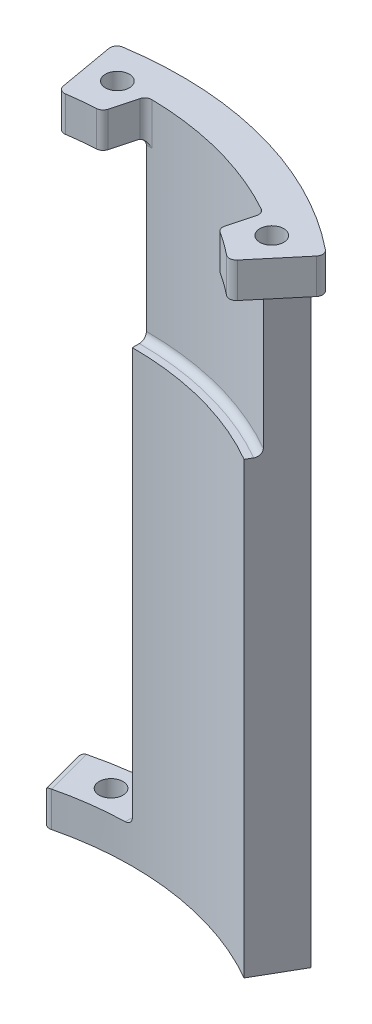
SolidWorks part; units mm, degrees
ref_plane "Front Plane" through (0, 0, 0) normal (0, 0, 1) x (1, 0, 0)
ref_plane "Top Plane" through (0, 0, 0) normal (0, 1, 0) x (1, 0, 0)
ref_plane "Right Plane" through (0, 0, 0) normal (1, 0, 0) x (0, 0, -1)
sketch "Sketch1" plane through (0, 0, 0) normal (0, 1, 0) x (1, 0, 0)
  line L0 (0, 50.5) -> (0, 0) construction
  line L1 (0, 0) -> (25.25, 43.7343) construction
  line L2 (0, 50.5) -> (0, 43.5)
  line L3 (21.75, 37.6721) -> (25.25, 43.7343)
  arc A0 (25.25, 43.7343) -> (0, 50.5) centre (0, 0) ccw
  arc A1 (21.75, 37.6721) -> (0, 43.5) centre (0, 0) ccw
  arc A2 (21.75, 37.6721) -> (0, 43.5) centre (0, 0) ccw construction
  dimension "D3" = 50.5
  dimension "D2" = 30
  dimension "D1" = 7
extrude "Boss-Extrude1" add sketch "Sketch1" along normal blind 94
sketch "Sketch2" plane through (0, 0, 0) normal (0, 1, 0) x (1, 0, 0)
  line L0 (-13.0704, 48.7793) -> (-11.2586, 42.0178)
  line L1 (-6.5916, 50.068) -> (-5.6779, 43.1279) construction
  line L2 (0, 50.5) -> (0, 43.5) construction
  line L3 (0, 50.5) -> (0, 43.5) construction
  line L4 (0, 50.5) -> (0, 43.5)
  line L5 (-6.1347, 46.5979) -> (0, 0) construction
  arc A0 (0, 50.5) -> (-13.0704, 48.7793) centre (0, 0) ccw
  circle A3 centre (-6.1347, 46.5979) radius 1.7
  arc A4 (-11.2586, 42.0178) -> (0, 43.5) centre (0, 0) cw
  dimension "D1" = 3.4
  dimension "D4" = 7
  dimension "D2" = 15
  dimension "D3" = 47
extrude "Boss-Extrude2" add sketch "Sketch2" along normal blind 5
sketch "Sketch4" plane through (0, 94, 0) normal (0, 1, 0) x (1, 0, 0)
  line L0 (0, 43.5) -> (0, 45.5)
  line L1 (21.75, 37.6721) -> (22.75, 39.4042)
  line L2 (0, 50.5) -> (0, 43.5)
  line L3 (21.75, 37.6721) -> (25.25, 43.7343)
  line L4 (0, 50.5) -> (0, 43.5) construction
  line L5 (21.75, 37.6721) -> (25.25, 43.7343) construction
  arc A0 (0, 45.5) -> (22.75, 39.4042) centre (0, 0) cw
  arc A2 (25.25, 43.7343) -> (0, 50.5) centre (0, 0) ccw
  arc A3 (21.75, 37.6721) -> (0, 43.5) centre (0, 0) ccw
  arc A4 (25.25, 43.7343) -> (0, 50.5) centre (0, 0) ccw construction
  arc A5 (21.75, 37.6721) -> (0, 43.5) centre (0, 0) ccw
  dimension "D2" = 5
  dimension "D1" = 0
extrude "Cut-Extrude2" cut sketch "Sketch4" against normal blind 30
sketch "Sketch3" plane through (0, 94, 0) normal (0, 1, 0) x (1, 0, 0)
  line L0 (22.75, 39.4042) -> (25.25, 43.7343) construction
  line L1 (0, 50.5) -> (0, 45.5) construction
  line L2 (0, 50.5) -> (0, 0) construction
  line L3 (0, 0) -> (25.25, 43.7343) construction
  line L4 (6.2653, 47.5894) -> (0, 0) construction
  line L5 (0, 0) -> (18.3688, 44.3462) construction
  arc A0 (0, 48) -> (24, 41.5692) centre (0, 0) cw construction
  arc A1 (25.25, 43.7343) -> (0, 50.5) centre (0, 0) ccw construction
  circle A2 centre (6.2653, 47.5894) radius 2
  circle A3 centre (18.3688, 44.3462) radius 2
  dimension "D1" = 4
  dimension "D5" = 48
  dimension "D2" = 30
  dimension "D3" = 7.5
  dimension "D4" = 7.5
  dimension "D6" = 15
extrude "Cut-Extrude1" [suppressed] cut sketch "Sketch3" against normal blind 8
fillet "Fillet1" radius 1 5 edges at (0, 5, -47) (-13.0704, 2.5, -48.7793) (-12.1645, 5, -45.3985) (-11.2586, 2.5, -42.0178) (11.7763, 64, -43.9496)
sketch "Sketch5" plane through (0, 94, 0) normal (0, 1, 0) x (1, 0, 0)
  line L0 (-8.7692, 49.7328) -> (0, 0) construction
  line L1 (0, 0) -> (32.4608, 38.6852) construction
  line L2 (22.75, 39.4042) -> (21.4043, 34.3818)
  line L3 (22.75, 39.4042) -> (25.25, 43.7343) construction
  line L4 (26.0329, 31.0248) -> (32.4608, 38.6852)
  line L5 (23.2298, 33.1757) -> (28.9656, 41.3672) construction
  line L6 (-8.7692, 49.7328) -> (-7.0328, 39.8847)
  line L7 (0, 45.5) -> (-1.3457, 40.4776)
  line L8 (-3.5298, 40.3459) -> (-4.4014, 50.3078) construction
  line L9 (0, 0) -> (11.7763, 43.9496) construction
  arc A0 (-8.7692, 49.7328) -> (32.4608, 38.6852) centre (0, 0) cw
  arc A1 (25.25, 43.7343) -> (0, 50.5) centre (0, 0) ccw construction
  arc A2 (-1, 50.4901) -> (-12.0823, 49.0333) centre (0, 0) ccw construction
  circle A3 centre (26.0977, 37.2714) radius 1.7
  arc A4 (22.75, 39.4042) -> (0, 45.5) centre (0, 0) ccw construction
  arc A5 (22.75, 39.4042) -> (0, 45.5) centre (0, 0) ccw
  arc A6 (21.4043, 34.3818) -> (26.0329, 31.0248) centre (0, 0) cw
  arc A7 (-7.0328, 39.8847) -> (-1.3457, 40.4776) centre (0, 0) cw
  circle A8 centre (-3.9656, 45.3269) radius 1.7
  circle A9 centre (0, 0) radius 45.5 construction
  dimension "D3" = 3.4
  dimension "D4" = 91
  dimension "D1" = 10
  dimension "D2" = 5
  dimension "D5" = 40
  dimension "D6" = 5
  dimension "D7" = 5
extrude "Boss-Extrude3" add sketch "Sketch5" against normal blind 5
fillet "Fillet2" radius 1 8 edges at (32.4608, 91.5, -38.6852) (26.0329, 91.5, -31.0248) (21.4043, 91.5, -34.3818) (22.75, 91.5, -39.4042) (-8.7692, 91.5, -49.7328) (-7.0328, 91.5, -39.8847) (-1.3457, 91.5, -40.4776) (0, 91.5, -45.5)
fillet "Fillet3" radius 1 4 edges at (24, 89, -41.5692) (22.4102, 89, -39.5984) (0.3914, 89, -45.4983) (0, 89, -48)
equation "\"D4@Sketch3\"=\"D3@Sketch3\""
equation "\"D3@Sketch3\"=\"D2@Sketch3\"/4"
equation "\"D7@Sketch5\"=\"D6@Sketch5\""
equation "\"D6@Sketch5\"=\"D1@Sketch5\"/2"
